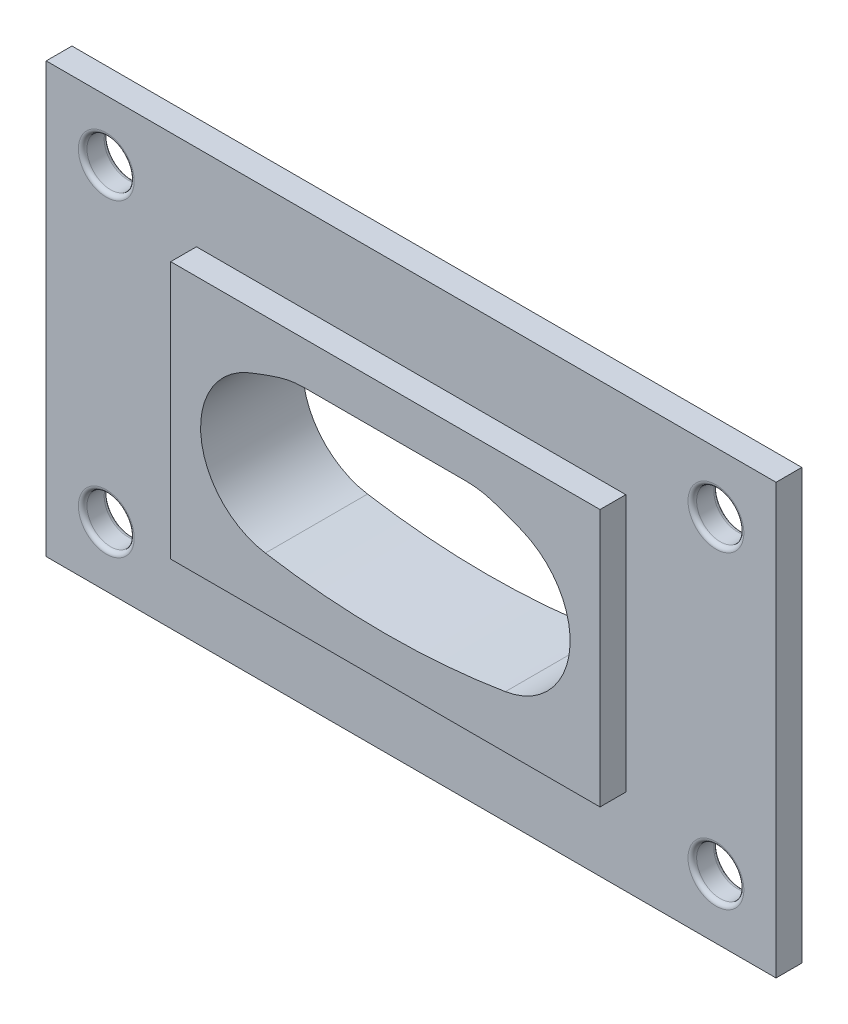
SolidWorks part; units mm, degrees
ref_plane "Front Plane" through (0, 0, 0) normal (0, 0, 1) x (1, 0, 0)
ref_plane "Top Plane" through (0, 0, 0) normal (0, 1, 0) x (1, 0, 0)
ref_plane "Right Plane" through (0, 0, 0) normal (1, 0, 0) x (0, 0, -1)
sketch "Sketch1" plane through (0, 0, 0) normal (0, 0, 1) x (1, 0, 0)
  line L0 (-12.5, 0) -> (12.5, 0) construction
  line L1 (0, 0) -> (0, 7868.0279) construction
  line L2 (-25.5, -13) -> (25.5, -13)
  line L3 (-25.5, -13) -> (-25.5, 13)
  line L4 (-25.5, 13) -> (25.5, 13)
  line L5 (25.5, -13) -> (25.5, 13)
  line L6 (-25.5, -13) -> (25.5, 13) construction
  line L7 (-25.5, 13) -> (25.5, -13) construction
  circle A0 centre (-12.5, 0) radius 8 construction
  circle A1 centre (12.5, 0) radius 8 construction
  arc A2 (-15.9979, 8.3) -> (-13.9784, -8.8807) centre (-12.518, 0) ccw
  arc A3 (15.9979, 8.3) -> (13.9784, -8.8807) centre (12.518, 0) cw
  arc A4 (-13.9784, -8.8807) -> (13.9784, -8.8807) centre (0, 76.121) ccw
  arc A5 (-15.9979, 8.3) -> (15.9979, 8.3) centre (0, -29.8571) cw
  point P4 (0, 0)
  point P11 (0, 0)
  point P17 (0, 11.518)
  dimension "D2" = 16
  dimension "D1" = 25
  dimension "D3" = 51
  dimension "D4" = 26
  dimension "D5" = 11.518
extrude "Boss-Extrude1" add sketch "Sketch1" along normal blind 5.9
sketch "Sketch2" plane through (0, 0, 0) normal (0, 0, -1) x (-1, 0, 0)
  line L0 (0, 0) -> (0, -50000) construction
  line L1 (0, 0) -> (50000, 0) construction
  circle A0 centre (-20.648, 8.08) radius 0.85
  arc A1 (13.9784, -8.8807) -> (15.9979, 8.3) centre (12.518, 0) ccw construction
  arc A2 (-15.9979, 8.3) -> (-13.9784, -8.8807) centre (-12.518, 0) ccw construction
  arc A3 (13.9784, -8.8807) -> (15.9979, 8.3) centre (12.518, 0) ccw construction
  arc A4 (-15.9979, 8.3) -> (-13.9784, -8.8807) centre (-12.518, 0) ccw construction
  circle A5 centre (20.648, 8.08) radius 0.85
  circle A6 centre (20.648, -8.08) radius 0.85
  circle A7 centre (-20.648, -8.08) radius 0.85
  dimension "D1" = 1.7
  dimension "D2" = 8.13
  dimension "D3" = 8.08
extrude "Cut-Extrude1" cut sketch "Sketch2" against normal blind 3
sketch "Sketch3" plane through (0, 0, 5.9) normal (0, 0, 1) x (1, 0, 0)
  line L0 (0, 0) -> (0, 50000) construction
  line L1 (-42.5, -25) -> (42.5, -25)
  line L2 (-42.5, -25) -> (-42.5, 25)
  line L3 (-42.5, 25) -> (42.5, 25)
  line L4 (42.5, -25) -> (42.5, 25)
  line L5 (-42.5, -25) -> (42.5, 25) construction
  line L6 (-42.5, 25) -> (42.5, -25) construction
  line L7 (0, 0) -> (50000, 0) construction
  circle A0 centre (-35.5, 18) radius 2.75
  circle A1 centre (35.5, 18) radius 2.75
  circle A2 centre (35.5, -18) radius 2.75
  circle A3 centre (-35.5, -18) radius 2.75
  arc A4 (-13.9784, -8.8807) -> (13.9784, -8.8807) centre (0, 76.121) ccw construction
  arc A5 (13.9784, -8.8807) -> (15.9979, 8.3) centre (12.518, 0) ccw construction
  arc A6 (15.9979, 8.3) -> (-15.9979, 8.3) centre (0, -29.8571) ccw construction
  arc A7 (-15.9979, 8.3) -> (-13.9784, -8.8807) centre (-12.518, 0) ccw construction
  arc A8 (-13.9784, -8.8807) -> (13.9784, -8.8807) centre (0, 76.121) ccw
  arc A9 (13.9784, -8.8807) -> (15.9979, 8.3) centre (12.518, 0) ccw
  arc A10 (15.9979, 8.3) -> (-15.9979, 8.3) centre (0, -29.8571) ccw
  arc A11 (-15.9979, 8.3) -> (-13.9784, -8.8807) centre (-12.518, 0) ccw
  point P0 (0, 0)
  dimension "D3" = 5.5
  dimension "D1" = 85
  dimension "D2" = 50
  dimension "D4" = 7
  dimension "D5" = 7
extrude "Boss-Extrude2" add sketch "Sketch3" along normal blind 3
sketch "Sketch4" plane through (0, 0, 8.9) normal (0, 0, 1) x (1, 0, 0)
  line L1 (-25, -15) -> (25, -15)
  line L2 (-25, -15) -> (-25, 15)
  line L3 (-25, 15) -> (25, 15)
  line L4 (25, -15) -> (25, 15)
  line L5 (-25, -15) -> (25, 15) construction
  line L6 (-25, 15) -> (25, -15) construction
  arc A0 (-13.9784, -8.8807) -> (13.9784, -8.8807) centre (0, 76.121) ccw construction
  arc A1 (13.9784, -8.8807) -> (15.9979, 8.3) centre (12.518, 0) ccw construction
  arc A2 (15.9979, 8.3) -> (-15.9979, 8.3) centre (0, -29.8571) ccw construction
  arc A3 (-15.9979, 8.3) -> (-13.9784, -8.8807) centre (-12.518, 0) ccw construction
  arc A4 (-13.9784, -8.8807) -> (13.9784, -8.8807) centre (0, 76.121) ccw
  arc A5 (13.9784, -8.8807) -> (15.9979, 8.3) centre (12.518, 0) ccw
  arc A6 (15.9979, 8.3) -> (-15.9979, 8.3) centre (0, -29.8571) ccw
  arc A7 (-15.9979, 8.3) -> (-13.9784, -8.8807) centre (-12.518, 0) ccw
  point P0 (0, 0)
  dimension "D1" = 50
  dimension "D2" = 30
extrude "Boss-Extrude3" add sketch "Sketch4" along normal blind 3
fillet "Fillet1" radius 0.5 8 edges at (-38.25, -18, 5.9) (-38.25, -18, 8.9) (38.25, -18, 5.9) (38.25, -18, 8.9) (32.75, 18, 5.9) (32.75, 18, 8.9) (-32.75, 18, 5.9) (-32.75, 18, 8.9)
sketch "Sketch6" plane through (0, 0, 0) normal (0, 0, -1) x (-1, 0, 0)
  line L0 (-10.8501, 10.07) -> (10.8501, 10.07)
  line L1 (-25.5, 13) -> (25.5, 13) construction
  arc A0 (15.9979, 8.3) -> (-15.9979, 8.3) centre (0, -29.8571) ccw construction
  arc A1 (10.8501, 10.07) -> (-10.8501, 10.07) centre (0, -29.8571) ccw
  dimension "D1" = 2.93
extrude "Boss-Extrude4" add sketch "Sketch6" against normal up to surface (11.9 mm away) up to face at (0, 0, 11.9)
fillet "Fillet2" radius 10 2 edges at (10.8501, 10.07, 5.95) (-10.8501, 10.07, 5.95)
